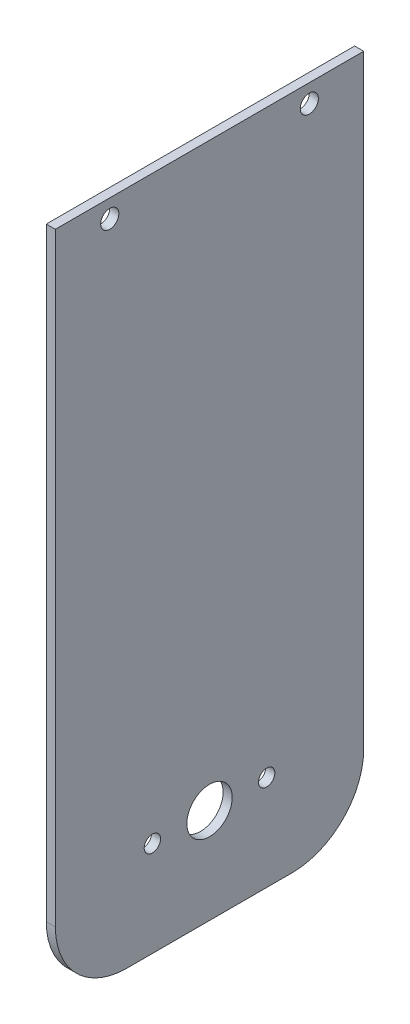
SolidWorks part; units mm, degrees
material "6061-T6 (SS)"
ref_plane "Front Plane" through (0, 0, 0) normal (0, 0, 1) x (1, 0, 0)
ref_plane "Top Plane" through (0, 0, 0) normal (0, 1, 0) x (1, 0, 0)
ref_plane "Right Plane" through (0, 0, 0) normal (1, 0, 0) x (0, 0, -1)
sketch "Sketch1" plane through (0, 0, 0) normal (1, 0, 0) x (0, 0, -1)
  line L0 (-53.975, -84.9275) -> (53.975, -84.9275) construction
  line L1 (-53.975, 118.2675) -> (53.975, 118.2675)
  line L2 (-53.975, 118.2675) -> (-53.975, -118.2675)
  line L3 (-53.975, -118.2675) -> (53.975, -118.2675)
  line L4 (53.975, 118.2675) -> (53.975, -118.2675)
  line L5 (-53.975, 118.2675) -> (53.975, -118.2675) construction
  line L6 (-53.975, -118.2675) -> (53.975, 118.2675) construction
  line L7 (-53.975, 111.9175) -> (53.975, 111.9175) construction
  line L8 (-34.925, 111.9175) -> (-34.925, 115.0925) construction
  line L9 (34.925, 111.9175) -> (34.925, 115.0925) construction
  line L10 (-53.975, 111.9175) -> (-34.925, 111.9175) construction
  line L11 (34.925, 111.9175) -> (53.975, 111.9175) construction
  circle A0 centre (0, -84.9275) radius 7.94
  circle A1 centre (20, -84.9275) radius 2.86
  circle A2 centre (-20, -84.9275) radius 2.86
  circle A3 centre (-34.925, 111.9175) radius 3.175
  circle A4 centre (34.925, 111.9175) radius 3.175
  point P0 (0, 0)
  point P20 (0, 0)
  point P23 (0, 0)
  dimension "D4" = 15.88
  dimension "D6" = 5.72
  dimension "D7" = 5.72
  dimension "D9" = 6.35
  dimension "D1" = 236.535
  dimension "D2" = 107.95
  dimension "D3" = 33.34
  dimension "D5" = 20
  dimension "D8" = 20
  dimension " 1in/2" = 6.35
  dimension "D10" = 19.05
  dimension "D11" = 19.05
extrude "Boss-Extrude1" add sketch "Sketch1" along normal blind 3.175
fillet "Fillet1" radius 25 2 edges at (1.5875, -118.2675, 53.975) (1.5875, -118.2675, -53.975)
